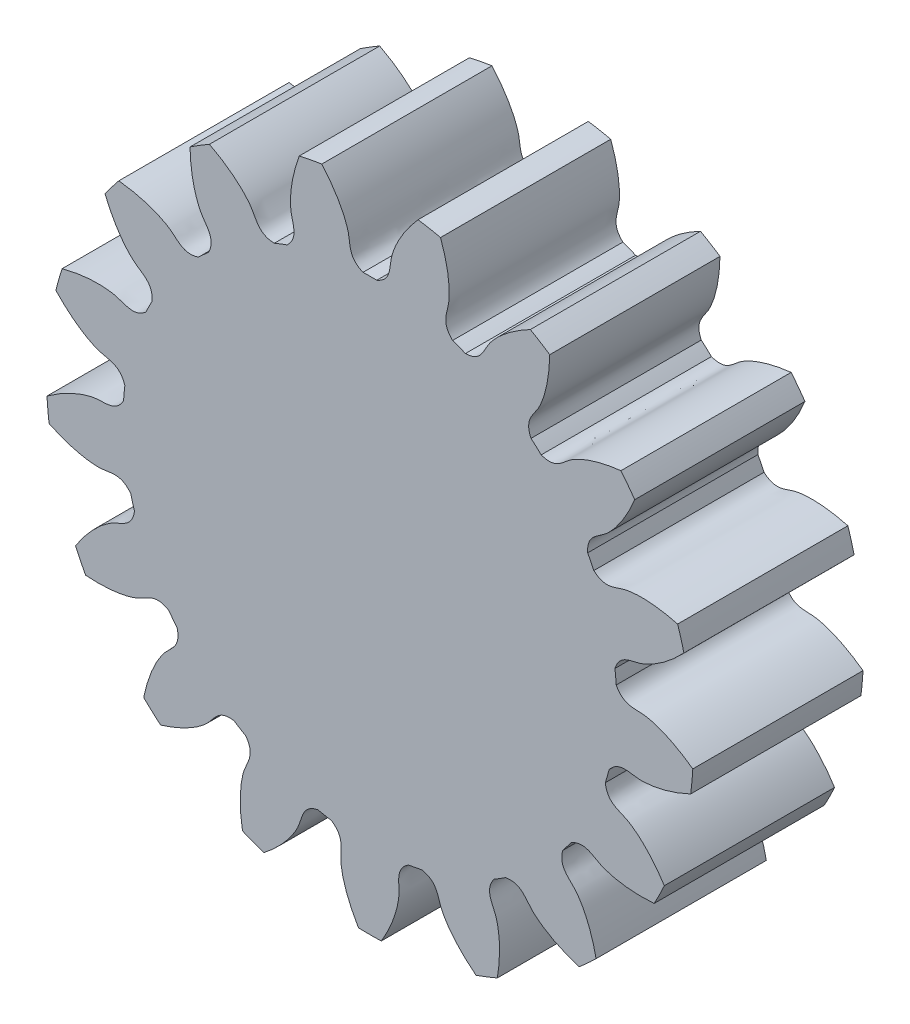
SolidWorks part; units mm, degrees
ref_plane "前视基准面" through (0, 0, 0) normal (0, 0, 1) x (1, 0, 0)
ref_plane "上视基准面" through (0, 0, 0) normal (0, 1, 0) x (1, 0, 0)
ref_plane "右视基准面" through (0, 0, 0) normal (1, 0, 0) x (0, 0, -1)
other "Configuration Table"
sketch "草图1" plane through (0, 0, 0) normal (0, 0, 1) x (1, 0, 0)
  circle A0 centre (0, 0) radius 19
extrude "凸台-拉伸1" add sketch "草图1" along normal blind 10
ref_axis "基准轴1" through (0, 0, -0.5) along (0, 0, 1)
sketch "草图2" plane through (0, 0, 0) normal (0, 0, 1) x (1, 0, 0)
  line L0 (0, 0) -> (0, 19) construction
  circle A0 centre (0, 0) radius 19 construction
  arc A1 (0.4034, 14.4944) -> (-0.4034, 14.4944) centre (0, 0) ccw
  arc A2 (6.2313, 21.4814) -> (-6.2313, 21.4814) centre (0, 0) ccw
  spline S0 degree 3 poles (0.4034, 14.4944) (1.2558, 14.8496) (1.1324, 15.5096) (1.2766, 16.1296) (1.29, 16.1823) (1.306, 16.2408) (1.3251, 16.3052) (1.3474, 16.3752) (1.3731, 16.4508) (1.4025, 16.5319) (1.4359, 16.6184) (1.4733, 16.7101) (1.5152, 16.8068) (1.5616, 16.9086) (1.6128, 17.0151) (1.669, 17.1264) (1.7304, 17.2421) (1.7972, 17.3621) (1.8696, 17.4863) (1.9478, 17.6145) (2.032, 17.7465) (2.1224, 17.8821) (2.2191, 18.0211) (2.3223, 18.1634) (2.4322, 18.3086) (2.5489, 18.4566) (2.6727, 18.6072) (2.8035, 18.7601) (2.9417, 18.9152) (3.0873, 19.0722) (3.2404, 19.2308) (3.4012, 19.3908) (3.5698, 19.552) (3.7462, 19.7141) (3.9307, 19.8769) (4.1233, 20.0401) (4.324, 20.2035) (4.533, 20.3667) (4.7503, 20.5295) (4.9761, 20.6917) (5.2103, 20.853) (5.453, 21.0131) (5.7916, 21.2269) (6.0532, 21.3811) (6.2313, 21.4814) knots 0 0 0 0 0.193883 0.199024 0.204851 0.211363 0.21856 0.226443 0.235011 0.244265 0.254205 0.264829 0.27614 0.288136 0.300817 0.314184 0.328236 0.342973 0.358397 0.374505 0.391299 0.408779 0.426944 0.445795 0.465331 0.485552 0.506459 0.528051 0.550329 0.573293 0.596941 0.621276 0.646296 0.672001 0.698392 0.725468 0.753229 0.781677 0.810809 0.840627 0.871131 0.90232 0.934195 1 1 1 1
  spline S1 degree 3 poles (-0.4034, 14.4944) (-1.2558, 14.8496) (-1.1324, 15.5096) (-1.2766, 16.1296) (-1.29, 16.1823) (-1.306, 16.2408) (-1.3251, 16.3052) (-1.3474, 16.3752) (-1.3731, 16.4508) (-1.4025, 16.5319) (-1.4359, 16.6184) (-1.4733, 16.7101) (-1.5152, 16.8068) (-1.5616, 16.9086) (-1.6128, 17.0151) (-1.669, 17.1264) (-1.7304, 17.2421) (-1.7972, 17.3621) (-1.8696, 17.4863) (-1.9478, 17.6145) (-2.032, 17.7465) (-2.1224, 17.8821) (-2.2191, 18.0211) (-2.3223, 18.1634) (-2.4322, 18.3086) (-2.5489, 18.4566) (-2.6727, 18.6072) (-2.8035, 18.7601) (-2.9417, 18.9152) (-3.0873, 19.0722) (-3.2404, 19.2308) (-3.4012, 19.3908) (-3.5698, 19.552) (-3.7462, 19.7141) (-3.9307, 19.8769) (-4.1233, 20.0401) (-4.324, 20.2035) (-4.533, 20.3667) (-4.7503, 20.5295) (-4.9761, 20.6917) (-5.2103, 20.853) (-5.453, 21.0131) (-5.7916, 21.2269) (-6.0532, 21.3811) (-6.2313, 21.4814) knots 0 0 0 0 0.193883 0.199024 0.204851 0.211363 0.21856 0.226443 0.235011 0.244265 0.254205 0.264829 0.27614 0.288136 0.300817 0.314184 0.328236 0.342973 0.358397 0.374505 0.391299 0.408779 0.426944 0.445795 0.465331 0.485552 0.506459 0.528051 0.550329 0.573293 0.596941 0.621276 0.646296 0.672001 0.698392 0.725468 0.753229 0.781677 0.810809 0.840627 0.871131 0.90232 0.934195 1 1 1 1
extrude "切除-拉伸1" cut sketch "草图2" along normal through all
pattern_circular "阵列(圆周)1" count 17 every 21.176 about axis through (0, 0, -0.5) along (0, 0, 1) of "切除-拉伸1"
sketch "草图3" plane through (0, 0, 0) normal (0, 0, 1) x (1, 0, 0)
  circle A0 centre (0, 0) radius 17 construction
  dimension "Dn" = 34
